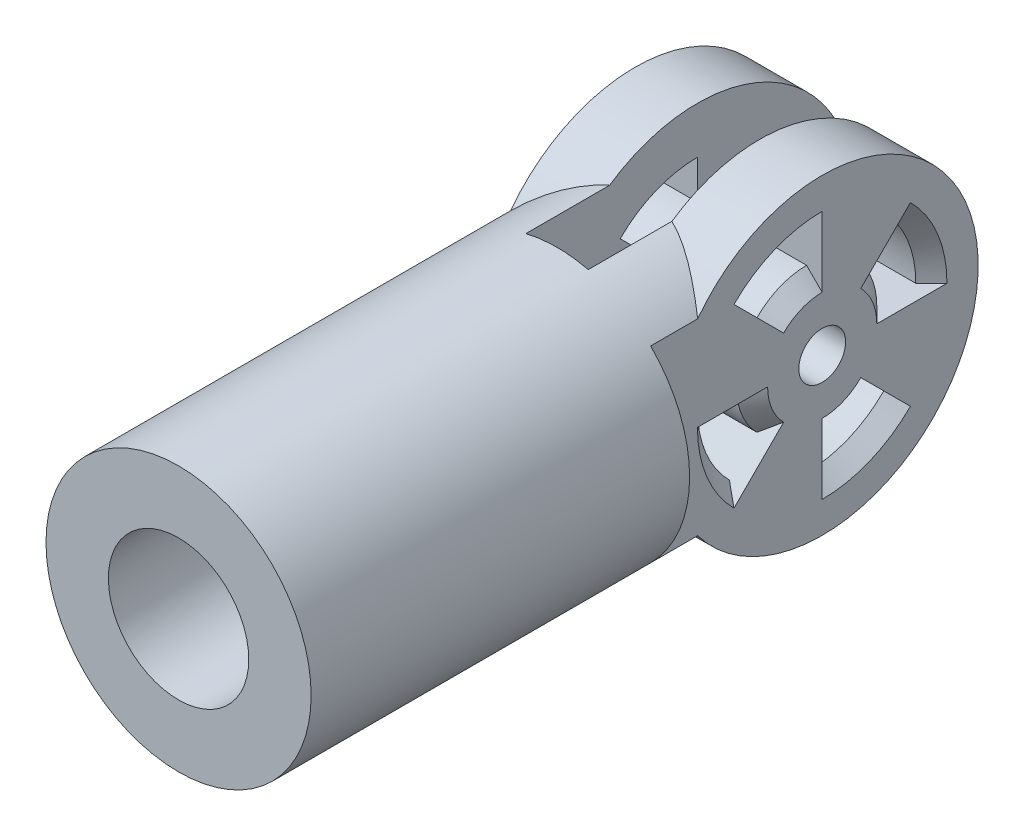
SolidWorks part; units mm, degrees
ref_plane "Спереди" through (0, 0, 0) normal (0, 0, 1) x (1, 0, 0)
ref_plane "Сверху" through (0, 0, 0) normal (0, 1, 0) x (1, 0, 0)
ref_plane "Справа" through (0, 0, 0) normal (1, 0, 0) x (0, 0, -1)
sketch "Sketch1" plane through (0, 0, 0) normal (0, 0, 1) x (1, 0, 0)
  circle A0 centre (0, 0) radius 4.5
  circle A1 centre (0, 0) radius 8.5
  dimension "D1" = 9
  dimension "D2" = 4
extrude "Boss-Extrude1" add sketch "Sketch1" along normal blind 30
sketch "Sketch2" plane through (0, 0, 0) normal (1, 0, 0) x (0, 0, -1)
  circle A0 centre (5.2678, 0) radius 10
  dimension "D1" = 20
extrude "Boss-Extrude2" add sketch "Sketch2" along normal mid plane 12
sketch "Sketch4" plane through (-6, 0, 0) normal (-1, 0, 0) x (0, 0, 1)
  circle A0 centre (-5.2678, 0) radius 1.5
  dimension "D1" = 3
extrude "Cut-Extrude1" cut sketch "Sketch4" against normal mid plane 34
sketch "Sketch5" plane through (0, 0, 0) normal (1, 0, 0) x (0, 0, -1)
  line L1 (16.2678, 11) -> (-5.7322, 11)
  line L2 (16.2678, 11) -> (16.2678, -11)
  line L3 (16.2678, -11) -> (-5.7322, -11)
  line L4 (-5.7322, 11) -> (-5.7322, -11)
  line L5 (16.2678, 11) -> (-5.7322, -11) construction
  line L6 (16.2678, -11) -> (-5.7322, 11) construction
  point P0 (5.2678, 0)
  dimension "D1" = 22
extrude "Cut-Extrude2" cut sketch "Sketch5" against normal mid plane 4
sketch "Sketch6" plane through (-6, 0, 0) normal (-1, 0, 0) x (0, 0, 1)
  line L1 (-16.2678, -11) -> (5.7322, -11)
  line L2 (-16.2678, -11) -> (-16.2678, 11)
  line L3 (-16.2678, 11) -> (5.7322, 11)
  line L4 (5.7322, -11) -> (5.7322, 11)
  line L5 (-16.2678, -11) -> (5.7322, 11) construction
  line L6 (-16.2678, 11) -> (5.7322, -11) construction
  point P0 (-5.2678, 0)
  dimension "D1" = 22
extrude "Cut-Extrude3" cut sketch "Sketch6" along normal blind 10
sketch "Sketch7" plane through (6, 0, 0) normal (1, 0, 0) x (0, 0, -1)
  line L1 (16.2678, 11) -> (-5.7322, 11)
  line L2 (16.2678, 11) -> (16.2678, -11)
  line L3 (16.2678, -11) -> (-5.7322, -11)
  line L4 (-5.7322, 11) -> (-5.7322, -11)
  line L5 (16.2678, 11) -> (-5.7322, -11) construction
  line L6 (16.2678, -11) -> (-5.7322, 11) construction
  point P0 (5.2678, 0)
  dimension "D1" = 22
extrude "Cut-Extrude4" cut sketch "Sketch7" along normal blind 11
sketch "Sketch8" plane through (6, 0, 0) normal (1, 0, 0) x (0, 0, -1)
  line L0 (5.2678, 0) -> (12.2678, 0)
  line L1 (5.2678, 0) -> (10.2176, -4.9497)
  line L2 (5.2678, 0) -> (5.2678, -7)
  line L3 (5.2678, 0) -> (10.2176, 4.9497)
  line L4 (5.2678, 0) -> (5.2678, 7)
  line L5 (5.2678, 0) -> (-1.7322, 0)
  line L6 (5.2678, 0) -> (0.3181, 4.9497)
  line L7 (5.2678, 0) -> (0.3181, -4.9497)
  circle A0 centre (5.2678, 0) radius 4.5
  circle A1 centre (5.2678, 0) radius 7
  arc A2 (-2.7165, -6.0208) -> (-2.7165, 6.0208) centre (5.2678, 0) ccw construction
  circle A3 centre (5.2678, 0) radius 1.5 construction
  dimension "D1" = 3
  dimension "D2" = 3
extrude "Cut-Extrude5" cut sketch "Sketch8" against normal blind 12 contours L0 A1 L3 A0 | L2 A1 L1 A0 | L5 A1 L7 A0 | L4 A1 L6 A0 region at (6, 2.1781, -10.5262) region at (6, -5.2584, -7.4459) region at (6, 5.2584, -3.0897) region at (6, -2.1781, -0.0095)
chamfer "Chamfer1" distance 1 angle 45 16 edges at (6, -2.6788, 1.1993) (6, -6.4672, -7.9466) (6, 2.6788, -11.735) (6, 6.4672, -2.589) (-6, 6.4672, -2.589) (-6, 2.6788, -11.735) (-6, -6.4672, -7.9466) (-6, -2.6788, 1.1993) (-6, -1.7221, -1.1104) (-6, -4.1575, -6.9899) (-6, 1.7221, -9.4253) (-6, 4.1575, -3.5458) (6, 4.1575, -3.5458) (6, -1.7221, -1.1104) (6, -4.1575, -6.9899) (6, 1.7221, -9.4253)
